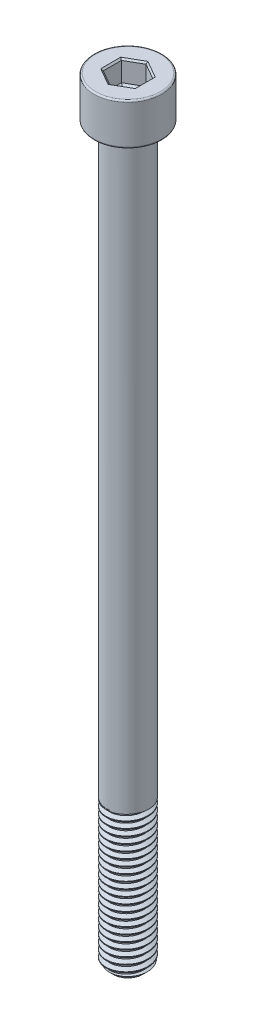
SolidWorks part; units mm, degrees
material "AISI Type A2 Tool Steel"
ref_plane "Front Plane" through (0, 0, 0) normal (0, 0, 1) x (1, 0, 0)
ref_plane "Top Plane" through (0, 0, 0) normal (0, 1, 0) x (1, 0, 0)
ref_plane "Right Plane" through (0, 0, 0) normal (1, 0, 0) x (0, 0, -1)
sketch "Sketch1" plane through (0, 0, 0) normal (0, 1, 0) x (1, 0, 0)
  circle A0 centre (0, 0) radius 4
  dimension "D1" = 8
extrude "Boss-Extrude1" add sketch "Sketch1" along normal blind 28
thread "Thread1" pitch 1.25 method cut profile "Thread Profile1" start angle 0, offset 2, length 0, pitch 1.25, diameter 8
ref_plane "Plane1" through (-4, 30, 0) normal (0, 0, 1) x (-1, 0, 0)
sketch "Thread Profile1" plane through (-4, 30, 0) normal (0, 0, 1) x (-1, 0, 0)
  line L0 (0, 0) -> (0, 1.25) construction
  line L11 (0, 0) -> (0, 1.0937)
  line L12 (0, 1.0937) -> (-0.6766, 0.7031)
  line L13 (-0.6766, 0.7031) -> (-0.6766, 0.3906)
  line L15 (-0.6766, 0.3906) -> (0, 0)
  line L17 (-0.6766, 0.5469) -> (0, 0.5469) construction
  point P2 (0, 0)
  dimension "Pitch" = 1.25
  dimension "Profile_Angle" = 60
  dimension "Profile_Land" = 0.3125
  dimension "Profile_Height" = 0.6766
sketch "Sketch2" plane through (0, 28, 0) normal (0, 1, 0) x (1, 0, 0)
  circle A0 centre (0, 0) radius 4
  dimension "D1" = 8
extrude "Boss-Extrude2" add sketch "Sketch2" along normal blind 112
sketch "Sketch5" plane through (0, 140, 0) normal (0, 1, 0) x (1, 0, 0)
  circle A0 centre (0, 0) radius 6.5
  dimension "D1" = 13
extrude "Boss-Extrude3" add sketch "Sketch5" along normal blind 8
sketch "Sketch6" plane through (0, 0, 0) normal (0, 0, 1) x (1, 0, 0)
  line L0 (0, 0) -> (0, 0.7245) construction
  line L1 (0, 0) -> (4.01, 0) construction
  line L2 (4.01, 0) -> (4.01, 1.2)
  line L3 (4.01, 1.2) -> (2.81, 0)
  line L4 (2.81, 0) -> (4.01, 0)
  dimension "D1" = 1.2
  dimension "D2" = 45
  dimension "D3" = 4.01
revolve "Cut-Revolve1" cut sketch "Sketch6" angle 360 about L0
fillet "Fillet1" radius 0.3 2 edges at (0, 140, 6.5) (0, 148, 6.5)
sketch "Sketch7" plane through (0, 148, 0) normal (0, 1, 0) x (1, 0, 0)
  line L1 (0, 3.4641) -> (-3, 1.7321)
  line L2 (-3, 1.7321) -> (-3, -1.7321)
  line L3 (-3, -1.7321) -> (0, -3.4641)
  line L4 (0, -3.4641) -> (3, -1.7321)
  line L5 (3, -1.7321) -> (3, 1.7321)
  line L6 (3, 1.7321) -> (0, 3.4641)
  circle A0 centre (0, 0) radius 3 construction
  dimension "D1" = 6
extrude "Cut-Extrude1" cut sketch "Sketch7" against normal blind 4
chamfer "Chamfer1" distance 0.3 angle 45 6 edges at (-3, 148, 0) (-1.5, 148, 2.5981) (1.5, 148, 2.5981) (3, 148, 0) (1.5, 148, -2.5981) (-1.5, 148, -2.5981)
sketch "Sketch8" plane through (0, 144, 0) normal (0, 1, 0) x (1, 0, 0)
  line L1 (0, 3.4641) -> (-3, 1.7321)
  line L2 (-3, 1.7321) -> (-3, -1.7321)
  line L3 (-3, -1.7321) -> (0, -3.4641)
  line L4 (0, -3.4641) -> (3, -1.7321)
  line L5 (3, -1.7321) -> (3, 1.7321)
  line L6 (3, 1.7321) -> (0, 3.4641)
  circle A0 centre (0, 0) radius 3 construction
extrude "Cut-Extrude2" cut sketch "Sketch8" against normal blind 0.4 draft 60
